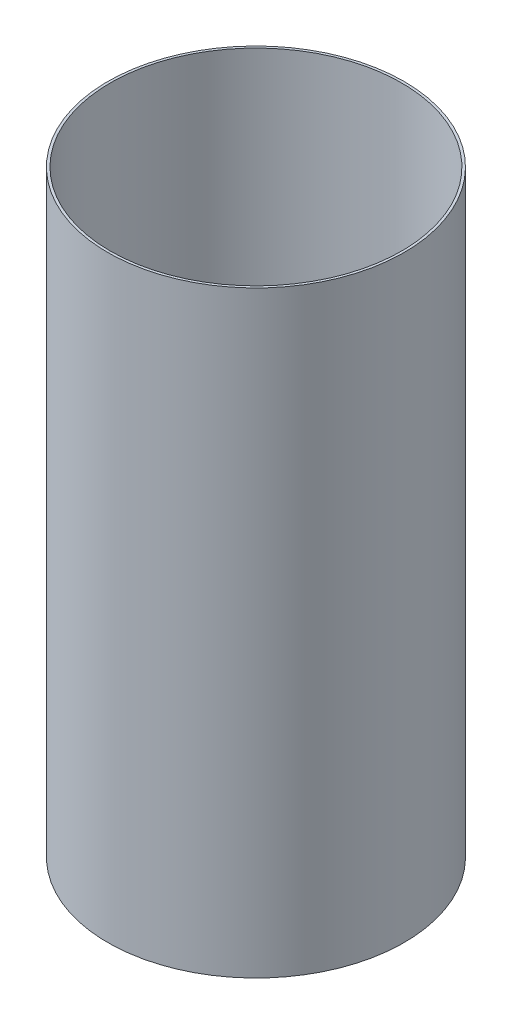
SolidWorks part; units mm, degrees
ref_plane "前视基准面" through (0, 0, 0) normal (0, 0, 1) x (1, 0, 0)
ref_plane "上视基准面" through (0, 0, 0) normal (0, 1, 0) x (1, 0, 0)
ref_plane "右视基准面" through (0, 0, 0) normal (1, 0, 0) x (0, 0, -1)
sketch "Sketch1" plane through (0, 0, 0) normal (0, 1, 0) x (1, 0, 0)
  circle A0 centre (0, 0) radius 74.295
  dimension "D1" = 148.59
extrude "Extrude-Thin2" add sketch "Sketch1" along normal blind 304.8 thin thin type one direction wall 1.27
sketch "Sketch2" plane through (0, 0, 0) normal (1, 0, 0) x (0, 0, -1)
  line L0 (0, 320.3693) -> (0, 0) construction
ref_plane "Plane1" through (74.295, 0, 0) normal (-1, 0, 0) x (0, 0, 1)
sketch "Sketch3" plane through (74.295, 0, 0) normal (-1, 0, 0) x (0, 0, 1)
  line L0 (0, 200320.3693) -> (0, -200000) construction
  circle A0 centre (0, 63.5) radius 3.302
  dimension "D1" = 6.604
  dimension "D2" = 63.5
extrude "Cut-Extrude2" cut sketch "Sketch3" along normal blind 2.54
pattern_circular "CirPattern2" count 3 every 120 about axis through (0, 320.3693, 0) along (0, -1, 0) of "Cut-Extrude2"
